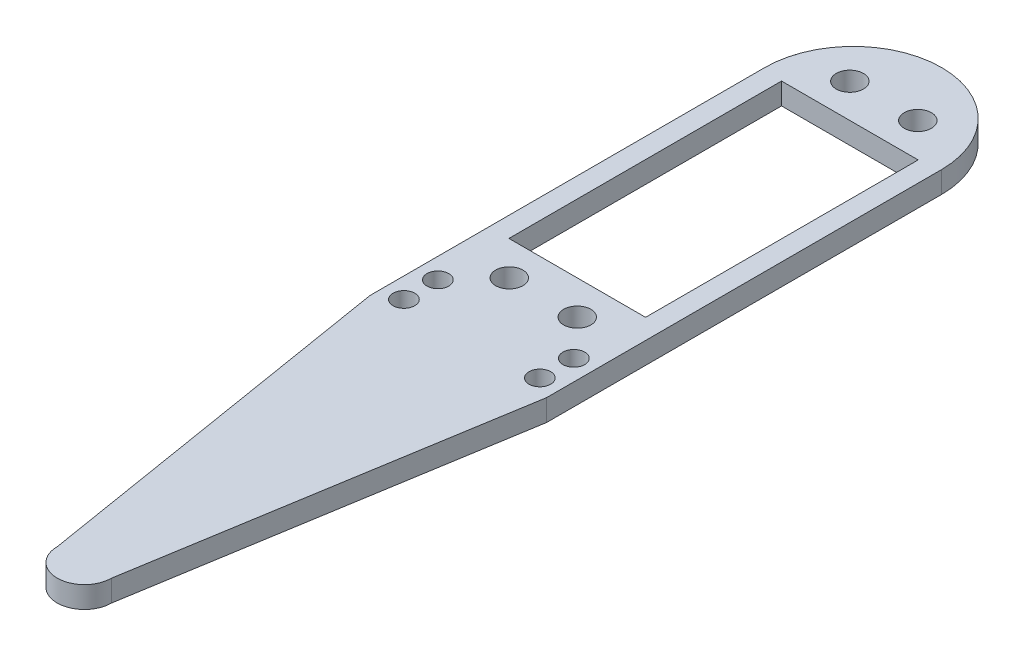
SolidWorks part; units mm, degrees
ref_plane "Front Plane" through (0, 0, 0) normal (0, 0, 1) x (1, 0, 0)
ref_plane "Top Plane" through (0, 0, 0) normal (0, 1, 0) x (1, 0, 0)
ref_plane "Right Plane" through (0, 0, 0) normal (1, 0, 0) x (0, 0, -1)
sketch "Sketch2" plane through (0, 0, 0) normal (0, 1, 0) x (1, 0, 0)
  line L0 (-13, 0) -> (-13, -58.1)
  line L1 (13, 0) -> (13, -58.1)
  line L2 (-13, -58.1) -> (-4, -113.1)
  line L3 (13, -58.1) -> (4, -113.1)
  line L4 (0, 13) -> (0, -117.1) construction
  line L5 (-4, -113.1) -> (4, -113.1) construction
  line L6 (-10.05, -0.5) -> (10.05, -0.5)
  line L7 (-10.05, -0.5) -> (-10.05, -40.6)
  line L8 (-10.05, -40.6) -> (10.05, -40.6)
  line L9 (10.05, -0.5) -> (10.05, -40.6)
  line L10 (-10.05, -0.5) -> (10.05, -40.6) construction
  line L11 (-10.05, -40.6) -> (10.05, -0.5) construction
  arc A0 (13, 0) -> (-13, 0) centre (0, 0) ccw
  arc A1 (-4, -113.1) -> (4, -113.1) centre (0, -113.1) ccw
  circle A2 centre (-5, 4.5) radius 2
  circle A4 centre (-5, -45.6) radius 2
  circle A5 centre (5, -45.6) radius 2
  circle A6 centre (5, 4.5) radius 2
  point P15 (0, -20.55)
  dimension "D1" = 4
  dimension "D8" = 13
  dimension "D10" = 4
  dimension "D2" = 50.1
  dimension "D3" = 5
  dimension "D4" = 4.5
  dimension "D5" = 40.1
  dimension "D6" = 20.1
  dimension "D7" = 5
  dimension "D9" = 55
  dimension "D11" = 12.5
extrude "Boss-Extrude1" add sketch "Sketch2" along normal blind 3.175
sketch "Sketch3" plane through (0, 3.175, 0) normal (0, 1, 0) x (1, 0, 0)
  circle A0 centre (10, -56.1) radius 1.6 construction
  circle A1 centre (10, -51.1) radius 1.6 construction
  circle A2 centre (-10, -56.1) radius 1.6 construction
  circle A3 centre (-10, -51.1) radius 1.6 construction
  circle A4 centre (10, -56.1) radius 1.6
  circle A5 centre (10, -51.1) radius 1.6
  circle A6 centre (-10, -56.1) radius 1.6
  circle A7 centre (-10, -51.1) radius 1.6
extrude "Cut-Extrude1" cut sketch "Sketch3" against normal through all both and the other way through all
